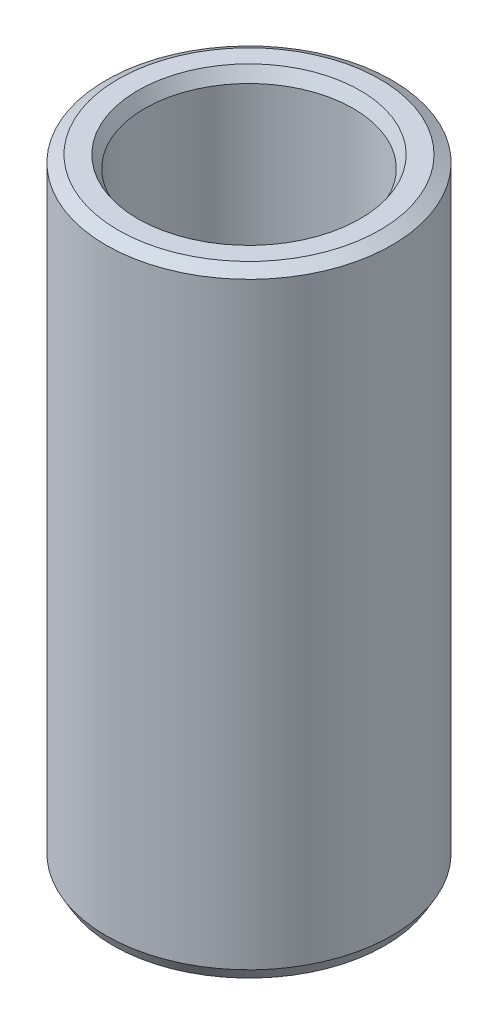
SolidWorks part; units mm, degrees
ref_plane "Front Plane" through (0, 0, 0) normal (0, 0, 1) x (1, 0, 0)
ref_plane "Top Plane" through (0, 0, 0) normal (0, 1, 0) x (1, 0, 0)
ref_plane "Right Plane" through (0, 0, 0) normal (1, 0, 0) x (0, 0, -1)
sketch "Sketch1" plane through (0, 0, 0) normal (0, 1, 0) x (1, 0, 0)
  circle A0 centre (0, 0) radius 15
  dimension "SLEEVE_OD" = 30
extrude "Boss-Extrude1" add sketch "Sketch1" along normal blind 64.7549
sketch "Sketch2" plane through (0, 0, 0) normal (0, 1, 0) x (1, 0, 0)
  circle A0 centre (0, 0) radius 10.936
  dimension "BORE_D" = 21.8721
extrude "Cut-Extrude1" cut sketch "Sketch2" along normal through all
chamfer "Chamfer1" distance 0.7319 angle 60 4 edges at (0, 64.7549, 10.936) (0, 0, 10.936) (0, 0, 15) (0, 64.7549, 15) first distance on face at (0, 64.7549, 10.936) first distance on face at (0, 0, 10.936) first distance on face at (0, 64.7549, 15)
